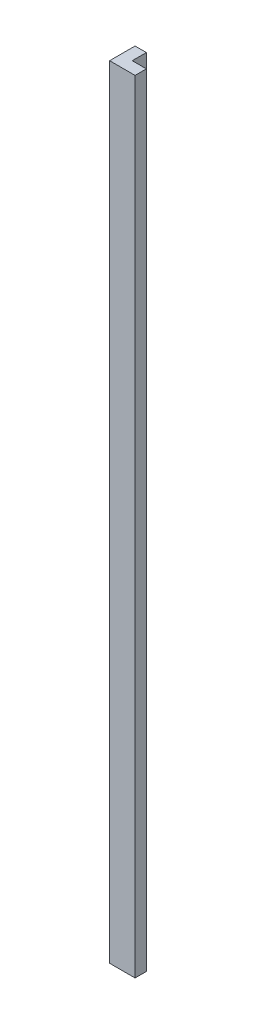
SolidWorks part; units mm, degrees
ref_plane "Front" through (0, 0, 0) normal (0, 0, 1) x (1, 0, 0)
ref_plane "Top" through (0, 0, 0) normal (0, 1, 0) x (1, 0, 0)
ref_plane "Right" through (0, 0, 0) normal (1, 0, 0) x (0, 0, -1)
sketch "Sketch1" plane through (0, 0, 0) normal (0, 1, 0) x (1, 0, 0)
  line L0 (0, 0) -> (0, 228.6)
  line L1 (0, 228.6) -> (101.6, 228.6)
  line L2 (101.6, 228.6) -> (101.6, 101.6)
  line L3 (101.6, 101.6) -> (228.6, 101.6)
  line L4 (228.6, 101.6) -> (228.6, 0)
  line L5 (228.6, 0) -> (0, 0)
  dimension "D1" = 101.6
  dimension "D2" = 228.6
extrude "Boss-Extrude1" add sketch "Sketch1" along normal blind 7023.1
